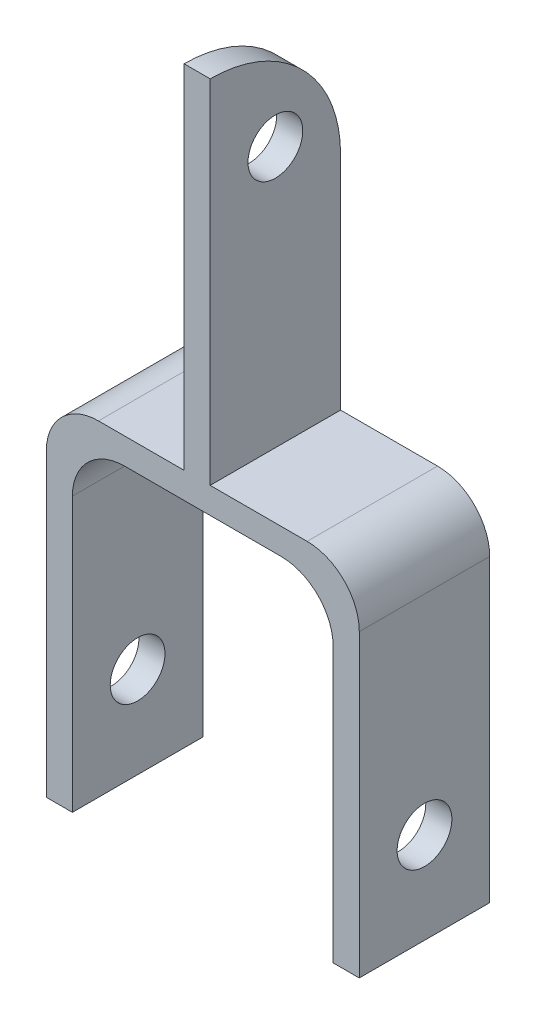
SolidWorks part; units mm, degrees
material "1060 Alloy"
ref_plane "Front Plane" through (0, 0, 0) normal (0, 0, 1) x (1, 0, 0)
ref_plane "Top Plane" through (0, 0, 0) normal (0, 1, 0) x (1, 0, 0)
ref_plane "Right Plane" through (0, 0, 0) normal (1, 0, 0) x (0, 0, -1)
sketch "Sketch1" plane through (0, 0, 0) normal (0, 0, 1) x (1, 0, 0)
  line L1 (0, 0) -> (2.54, 0)
  line L2 (2.54, 0) -> (2.54, 31.75)
  line L3 (2.54, 31.75) -> (27.94, 31.75)
  line L4 (27.94, 31.75) -> (27.94, 0)
  line L5 (27.94, 0) -> (30.48, 0)
  line L8 (30.48, 34.29) -> (15.9578, 34.29)
  line L9 (15.9578, 34.29) -> (15.9578, 68.58)
  line L10 (15.9578, 68.58) -> (13.4178, 68.58)
  line L11 (13.4178, 68.58) -> (13.4178, 34.29)
  line L12 (13.4178, 34.29) -> (0, 34.29)
  line L14 (0, 34.29) -> (0, 0)
  line L15 (30.48, 34.29) -> (30.48, 0)
  dimension "D1" = 34.29
  dimension "D2" = 34.29
  dimension "D3" = 2.54
  dimension "D4" = 2.54
  dimension "D5" = 30.48
  dimension "D6" = 15.9578
extrude "Boss-Extrude1" add sketch "Sketch1" along normal blind 12.7
sketch "Sketch2" plane through (0, 0, 0) normal (1, 0, 0) x (0, 0, -1)
  point P0 (-6.35, 59.69)
  point P1 (-6.35, 8.89)
  dimension "D1" = 59.69
  dimension "D2" = 6.35
  dimension "D3" = 6.35
  dimension "D4" = 8.89
hole_wizard "#0000 Clearance Hole1" positions "Sketch3" profile "Sketch4" hole size "#0000" standard "ANSI Inch" end condition through all
sketch "Sketch3" plane through (0, 0, 0) normal (1, 0, 0) x (0, 0, -1)
  point P1 (-6.35, 59.69)
  point P4 (-6.35, 59.69)
  point P6 (-6.35, 8.89)
sketch "Sketch4" plane through (0, 59.69, 6.35) normal (0, 1, 0) x (0, 0, 1)
  line L0 (0, 0) -> (0, 30.48)
  line L1 (0, 30.48) -> (2.667, 30.48)
  line L2 (2.667, 30.48) -> (2.667, 0)
  line L5 (2.667, 0) -> (0, 0)
  line L11 (0, -6.35) -> (0, 107.95) construction
  dimension "Thru Hole Dia." = 5.334
  dimension "Thru Hole Depth" = 30.48
fillet "Fillet1" radius 5.08 4 edges at (0, 34.29, 6.35) (30.48, 34.29, 6.35) (2.54, 31.75, 6.35) (27.94, 31.75, 6.35)
sketch "Sketch5" plane through (0, 0, 0) normal (0, 0, -1) x (-1, 0, 0)
  line L0 (-14.6878, 68.58) -> (-14.6878, 31.75)
  line L1 (-15.9578, 68.58) -> (-13.4178, 68.58) construction
  line L2 (-7.62, 31.75) -> (-22.86, 31.75) construction
fillet "Fillet2" radius 12.7 1 edges at (14.6878, 68.58, 0)
